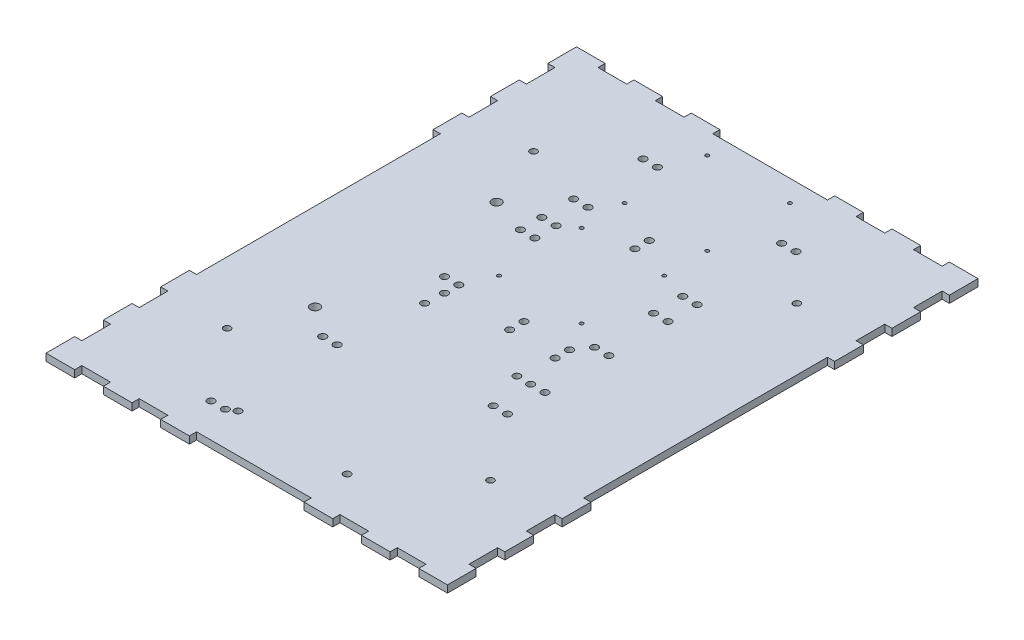
SolidWorks part; units mm, degrees
material "Acrylic (Medium-high impact)"
ref_plane "Front Plane" through (0, 0, 0) normal (0, 0, 1) x (1, 0, 0)
ref_plane "Top Plane" through (0, 0, 0) normal (0, 1, 0) x (1, 0, 0)
ref_plane "Right Plane" through (0, 0, 0) normal (1, 0, 0) x (0, 0, -1)
sketch "Sketch1" plane through (0, 0, 0) normal (0, 1, 0) x (1, 0, 0)
  line L0 (0, 209.55) -> (0, 196.85)
  line L1 (0, 0) -> (177.8, 0)
  line L2 (0, 0) -> (0, 234.95)
  line L3 (0, 234.95) -> (177.8, 234.95)
  line L4 (177.8, 0) -> (177.8, 234.95)
  line L5 (0, 234.95) -> (3.175, 234.95)
  line L6 (0, 234.95) -> (0, 0)
  line L7 (0, 0) -> (3.175, 0)
  line L8 (3.175, 234.95) -> (3.175, 0)
  line L9 (177.8, 234.95) -> (174.625, 234.95)
  line L10 (177.8, 234.95) -> (177.8, 0)
  line L11 (177.8, 0) -> (174.625, 0)
  line L12 (174.625, 234.95) -> (174.625, 0)
  line L13 (0, 234.95) -> (3.175, 234.95)
  line L14 (0, 234.95) -> (0, 222.25)
  line L15 (0, 222.25) -> (3.175, 222.25)
  line L16 (3.175, 234.95) -> (3.175, 222.25)
  line L17 (0, 209.55) -> (3.175, 209.55)
  line L18 (3.175, 209.55) -> (3.175, 196.85)
  line L19 (0, 196.85) -> (3.175, 196.85)
  line L20 (0, 184.15) -> (0, 171.45)
  line L21 (0, 184.15) -> (3.175, 184.15)
  line L22 (3.175, 184.15) -> (3.175, 171.45)
  line L23 (0, 171.45) -> (3.175, 171.45)
  line L24 (0, 117.475) -> (177.8, 117.475) construction
  line L25 (88.9, 234.95) -> (88.9, 0) construction
  line L26 (177.8, 171.45) -> (174.625, 171.45)
  line L27 (174.625, 184.15) -> (174.625, 171.45)
  line L28 (177.8, 184.15) -> (174.625, 184.15)
  line L29 (177.8, 184.15) -> (177.8, 171.45)
  line L30 (177.8, 196.85) -> (174.625, 196.85)
  line L31 (174.625, 209.55) -> (174.625, 196.85)
  line L32 (177.8, 209.55) -> (174.625, 209.55)
  line L33 (174.625, 234.95) -> (174.625, 222.25)
  line L34 (177.8, 222.25) -> (174.625, 222.25)
  line L35 (177.8, 234.95) -> (177.8, 222.25)
  line L36 (177.8, 234.95) -> (174.625, 234.95)
  line L37 (177.8, 234.95) -> (177.8, 0)
  line L38 (177.8, 234.95) -> (174.625, 234.95)
  line L39 (177.8, 209.55) -> (177.8, 196.85)
  line L40 (177.8, 25.4) -> (177.8, 38.1)
  line L41 (177.8, 0) -> (174.625, 0)
  line L42 (177.8, 0) -> (174.625, 0)
  line L43 (177.8, 0) -> (177.8, 12.7)
  line L44 (177.8, 12.7) -> (174.625, 12.7)
  line L45 (174.625, 0) -> (174.625, 12.7)
  line L46 (177.8, 25.4) -> (174.625, 25.4)
  line L47 (174.625, 25.4) -> (174.625, 38.1)
  line L48 (177.8, 38.1) -> (174.625, 38.1)
  line L49 (177.8, 50.8) -> (177.8, 63.5)
  line L50 (177.8, 50.8) -> (174.625, 50.8)
  line L51 (174.625, 50.8) -> (174.625, 63.5)
  line L52 (177.8, 63.5) -> (174.625, 63.5)
  line L53 (0, 63.5) -> (3.175, 63.5)
  line L54 (3.175, 50.8) -> (3.175, 63.5)
  line L55 (0, 50.8) -> (3.175, 50.8)
  line L56 (0, 50.8) -> (0, 63.5)
  line L57 (0, 38.1) -> (3.175, 38.1)
  line L58 (3.175, 25.4) -> (3.175, 38.1)
  line L59 (0, 25.4) -> (3.175, 25.4)
  line L60 (3.175, 0) -> (3.175, 12.7)
  line L61 (0, 12.7) -> (3.175, 12.7)
  line L62 (0, 0) -> (0, 12.7)
  line L63 (0, 0) -> (3.175, 0)
  line L64 (177.8, 0) -> (174.625, 0)
  line L65 (0, 0) -> (3.175, 0)
  line L66 (0, 0) -> (177.8, 0)
  line L67 (0, 25.4) -> (0, 38.1)
  dimension "D1" = 234.95
  dimension "D2" = 177.8
  dimension "D3" = 3.175
  dimension "D4" = 3.175
  dimension "D5" = 12.7
  dimension "D6" = 3.175
  dimension "D7" = 3
extrude "Boss-Extrude1" add sketch "Sketch1" along normal blind 3.175 contours L6 L55 L8 L53 | L6 L59 L8 L57 | L61 L2 L1 L8 | L6 L23 L8 L21 | L0 L19 L8 L17 | L6 L15 L8 L3 | L4 L44 L12 L1 | L37 L48 L12 L46 | L37 L52 L12 L50 | L34 L10 L3 L12 | L10 L32 L12 L30 | L10 L28 L12 L26 | L52 L12 L26 L27 L28 L30 L31 L32 L34 L33 L3 L8 L1 L45 L44 L46 L47 L48 L50 L51 region at (1.5875, 0, -203.2) region at (1.5875, 0, -228.6) region at (88.9, 0, -117.475) region at (1.5875, 0, -177.8) region at (1.5875, 0, -57.15) region at (176.2125, 0, -228.6) region at (1.5875, 0, -31.75) region at (176.2125, 0, -203.2) region at (1.5875, 0, -6.35) region at (176.2125, 0, -177.8) region at (176.2125, 0, -57.15) region at (176.2125, 0, -6.35) region at (176.2125, 0, -31.75)
sketch "Sketch2" plane through (0, 3.175, 0) normal (0, 1, 0) x (1, 0, 0)
  line L0 (3.175, 12.7) -> (30.5816, 12.7)
  line L1 (30.5816, 0) -> (30.5816, 234.95)
  line L3 (0, 0) -> (177.8, 0) construction
  line L4 (0, 234.95) -> (177.8, 234.95) construction
  line L5 (30.5816, 0) -> (30.5816, 14.0716)
  line L6 (30.5816, 14.0716) -> (30.5816, 49.6316)
  line L7 (3.175, 117.475) -> (174.625, 117.475) construction
  line L8 (3.175, 171.45) -> (3.175, 63.5) construction
  line L9 (174.625, 171.45) -> (174.625, 63.5) construction
  line L10 (88.9, 234.95) -> (88.9, 0) construction
  circle A0 centre (30.5816, 49.6316) radius 1.524
  circle A1 centre (147.2184, 49.6316) radius 1.524
  circle A2 centre (147.2184, 185.3184) radius 1.524
  circle A3 centre (30.5816, 185.3184) radius 1.524
  dimension "D4" = 3.048
  dimension "D1" = 27.4066
  dimension "D2" = 14.0716
  dimension "D3" = 35.56
extrude "Cut-Extrude1" cut sketch "Sketch2" against normal blind 3.175 and the other way through all contours A3 L1 | A3 L1 | L1 A0 L6 | L6 A0 L1 | A1 | A2 region at (29.9348, 3.175, -49.6316) region at (29.9348, 3.175, -185.3184) region at (31.2284, 3.175, -185.3184) region at (31.2284, 3.175, -49.6316) region at (147.2184, 3.175, -49.6316) region at (147.2184, 3.175, -185.3184)
sketch "Sketch3" plane through (0, 3.175, 0) normal (0, 1, 0) x (1, 0, 0)
  line L0 (88.9, 234.95) -> (88.9, 0) construction
  line L1 (0, 234.95) -> (177.8, 234.95) construction
  line L2 (0, 0) -> (177.8, 0) construction
  line L4 (88.9, 234.95) -> (70.6, 234.95)
  line L5 (88.9, 234.95) -> (88.9, 222.25)
  line L6 (88.9, 222.25) -> (70.6, 222.25)
  line L7 (70.6, 234.95) -> (70.6, 222.25)
  line L8 (70.6, 222.25) -> (107.2, 222.25)
  line L9 (70.6, 222.25) -> (70.6, 185.65)
  line L10 (70.6, 185.65) -> (107.2, 185.65)
  line L11 (107.2, 222.25) -> (107.2, 185.65)
  line L12 (70.6, 166.6) -> (107.2, 166.6)
  line L13 (70.6, 166.6) -> (70.6, 130)
  line L14 (70.6, 130) -> (107.2, 130)
  line L15 (107.2, 166.6) -> (107.2, 130)
  circle A0 centre (70.6, 222.25) radius 0.8
  circle A1 centre (107.2, 222.25) radius 0.8
  circle A2 centre (70.6, 185.65) radius 0.8
  circle A3 centre (107.2, 185.65) radius 0.8
  circle A4 centre (70.6, 166.6) radius 0.8
  circle A5 centre (107.2, 166.6) radius 0.8
  circle A6 centre (70.6, 130) radius 0.8
  circle A7 centre (107.2, 130) radius 0.8
  dimension "D4" = 1.6
  dimension "D5" = 1.6
  dimension "D6" = 1.6
  dimension "D7" = 1.6
  dimension "D8" = 36.6
  dimension "D10" = 1.6
  dimension "D11" = 1.6
  dimension "D12" = 1.6
  dimension "D13" = 1.6
  dimension "D1" = 12.7
  dimension "D2" = 18.3
  dimension "D3" = 36.6
  dimension "D9" = 19.05
extrude "Cut-Extrude2" cut sketch "Sketch3" against normal blind 5.715 contours L8 A0 L7 | L7 A0 L9 | L9 A0 L8 | L8 A1 L11 | L11 A1 L8 | L10 A2 L9 | L9 A2 L10 | L11 A3 L10 | L10 A3 L11 | L13 A4 L12 | L12 A4 L13 | L12 A5 L15 | L15 A5 L12 | L14 A6 L13 | L13 A6 L14 | L15 A7 L14 | L14 A7 L15 region at (70.9395, 3.175, -222.5895) region at (70.2605, 3.175, -222.25) region at (70.9395, 3.175, -221.9105) region at (107.3132, 3.175, -222.3632) region at (106.8605, 3.175, -221.9105) region at (70.9395, 3.175, -185.9895) region at (70.4868, 3.175, -185.5368) region at (107.3132, 3.175, -185.5368) region at (106.8605, 3.175, -185.9895) region at (70.4868, 3.175, -166.7132) region at (70.9395, 3.175, -166.2605) region at (107.3132, 3.175, -166.7132) region at (106.8605, 3.175, -166.2605) region at (70.9395, 3.175, -130.3395) region at (70.4868, 3.175, -129.8868) region at (107.3132, 3.175, -129.8868) region at (106.8605, 3.175, -130.3395)
sketch "Sketch4" plane through (0, 3.175, 0) normal (0, 1, 0) x (1, 0, 0)
  line L0 (88.9, 0) -> (88.9, 20.32) construction
  line L1 (0, 0) -> (177.8, 0) construction
  line L2 (88.9, 20.32) -> (64.7319, 20.32) construction
  line L3 (64.7319, 20.32) -> (64.7319, 95.4532) construction
  line L4 (64.7319, 20.32) -> (113.0681, 20.32) construction
  line L5 (113.0681, 20.32) -> (113.0681, 102.9462) construction
  circle A0 centre (64.7319, 20.32) radius 1.5621
  circle A3 centre (113.0681, 20.32) radius 1.5621
  circle A4 centre (64.7319, 102.9462) radius 1.5621
  circle A5 centre (113.0681, 95.4532) radius 1.5621
  dimension "D3" = 3.1242
  dimension "D4" = 75.1332
  dimension "D9" = 3.1242
  dimension "D1" = 20.32
  dimension "D2" = 24.1681
  dimension "D6" = 48.3362
  dimension "D7" = 82.6262
extrude "Cut-Extrude3" cut sketch "Sketch4" against normal blind 10.16 contours A3 | A0 | A4 | A5 region at (64.7319, 3.175, -20.32) region at (113.0681, 3.175, -20.32) region at (64.7319, 3.175, -102.9462) region at (113.0681, 3.175, -95.4532)
sketch "Sketch5" plane through (0, 3.175, 0) normal (0, 1, 0) x (1, 0, 0)
  line L0 (88.9, 0) -> (88.9, 18.3402) construction
  line L1 (0, 0) -> (177.8, 0) construction
  line L3 (0, 0) -> (12.7, 0)
  line L4 (0, 0) -> (0, 3.175)
  line L5 (0, 3.175) -> (12.7, 3.175)
  line L6 (12.7, 0) -> (12.7, 3.175)
  line L10 (25.4, 3.175) -> (38.1, 3.175)
  line L11 (25.4, 0) -> (38.1, 0)
  line L12 (38.1, 0) -> (38.1, 3.175)
  line L13 (25.4, 0) -> (25.4, 3.175)
  line L14 (50.8, 3.175) -> (63.5, 3.175)
  line L15 (50.8, 0) -> (63.5, 0)
  line L16 (63.5, 0) -> (63.5, 3.175)
  line L17 (50.8, 0) -> (50.8, 3.175)
  line L18 (0, 3.175) -> (177.8, 3.175)
  line L19 (127, 0) -> (127, 3.175)
  line L20 (114.3, 0) -> (114.3, 3.175)
  line L21 (127, 0) -> (114.3, 0)
  line L22 (127, 3.175) -> (114.3, 3.175)
  line L23 (152.4, 0) -> (152.4, 3.175)
  line L24 (139.7, 0) -> (139.7, 3.175)
  line L25 (152.4, 0) -> (139.7, 0)
  line L26 (152.4, 3.175) -> (139.7, 3.175)
  line L27 (165.1, 0) -> (165.1, 3.175)
  line L28 (177.8, 3.175) -> (165.1, 3.175)
  line L29 (177.8, 0) -> (177.8, 3.175)
  line L30 (177.8, 0) -> (165.1, 0)
  line L63 (0, 63.5) -> (0, 50.8)
  line L64 (0, 50.8) -> (3.175, 50.8)
  line L65 (3.175, 50.8) -> (3.175, 38.1)
  line L66 (3.175, 38.1) -> (0, 38.1)
  line L67 (0, 38.1) -> (0, 25.4)
  line L68 (0, 25.4) -> (3.175, 25.4)
  line L69 (3.175, 25.4) -> (3.175, 12.7)
  line L70 (3.175, 12.7) -> (0, 12.7)
  line L71 (0, 12.7) -> (0, 0)
  line L72 (0, 0) -> (177.8, 0)
  line L73 (177.8, 0) -> (177.8, 12.7)
  line L74 (177.8, 12.7) -> (174.625, 12.7)
  line L75 (174.625, 12.7) -> (174.625, 25.4)
  line L76 (174.625, 25.4) -> (177.8, 25.4)
  line L77 (177.8, 25.4) -> (177.8, 38.1)
  line L78 (177.8, 38.1) -> (174.625, 38.1)
  line L79 (174.625, 38.1) -> (174.625, 50.8)
  line L80 (174.625, 50.8) -> (177.8, 50.8)
  line L81 (177.8, 50.8) -> (177.8, 63.5)
  line L82 (177.8, 63.5) -> (174.625, 63.5)
  line L83 (174.625, 63.5) -> (174.625, 171.45)
  line L84 (174.625, 171.45) -> (177.8, 171.45)
  line L85 (177.8, 171.45) -> (177.8, 184.15)
  line L86 (177.8, 184.15) -> (174.625, 184.15)
  line L87 (174.625, 184.15) -> (174.625, 196.85)
  line L88 (174.625, 196.85) -> (177.8, 196.85)
  line L89 (177.8, 196.85) -> (177.8, 209.55)
  line L90 (177.8, 209.55) -> (174.625, 209.55)
  line L91 (174.625, 209.55) -> (174.625, 222.25)
  line L92 (174.625, 222.25) -> (177.8, 222.25)
  line L93 (177.8, 222.25) -> (177.8, 234.95)
  line L94 (177.8, 234.95) -> (0, 234.95)
  line L95 (0, 234.95) -> (0, 222.25)
  line L96 (0, 222.25) -> (3.175, 222.25)
  line L97 (3.175, 222.25) -> (3.175, 209.55)
  line L98 (3.175, 209.55) -> (0, 209.55)
  line L99 (0, 209.55) -> (0, 196.85)
  line L100 (0, 196.85) -> (3.175, 196.85)
  line L101 (3.175, 196.85) -> (3.175, 184.15)
  line L102 (3.175, 184.15) -> (0, 184.15)
  line L103 (0, 184.15) -> (0, 171.45)
  line L104 (0, 171.45) -> (3.175, 171.45)
  line L105 (3.175, 171.45) -> (3.175, 63.5)
  line L106 (3.175, 63.5) -> (0, 63.5)
  line L107 (0, 63.5) -> (0, 50.8)
  line L108 (0, 50.8) -> (3.175, 50.8)
  line L109 (3.175, 50.8) -> (3.175, 38.1)
  line L110 (3.175, 38.1) -> (0, 38.1)
  line L111 (0, 38.1) -> (0, 25.4)
  line L112 (0, 25.4) -> (3.175, 25.4)
  line L113 (3.175, 25.4) -> (3.175, 12.7)
  line L114 (3.175, 12.7) -> (0, 12.7)
  line L115 (0, 12.7) -> (0, 0)
  line L116 (0, 0) -> (177.8, 0)
  line L117 (177.8, 0) -> (177.8, 12.7)
  line L118 (177.8, 12.7) -> (174.625, 12.7)
  line L119 (174.625, 12.7) -> (174.625, 25.4)
  line L120 (174.625, 25.4) -> (177.8, 25.4)
  line L121 (177.8, 25.4) -> (177.8, 38.1)
  line L122 (177.8, 38.1) -> (174.625, 38.1)
  line L123 (174.625, 38.1) -> (174.625, 50.8)
  line L124 (174.625, 50.8) -> (177.8, 50.8)
  line L125 (177.8, 50.8) -> (177.8, 63.5)
  line L126 (177.8, 63.5) -> (174.625, 63.5)
  line L127 (174.625, 63.5) -> (174.625, 171.45)
  line L128 (174.625, 171.45) -> (177.8, 171.45)
  line L129 (177.8, 171.45) -> (177.8, 184.15)
  line L130 (177.8, 184.15) -> (174.625, 184.15)
  line L131 (174.625, 184.15) -> (174.625, 196.85)
  line L132 (174.625, 196.85) -> (177.8, 196.85)
  line L133 (177.8, 196.85) -> (177.8, 209.55)
  line L134 (177.8, 209.55) -> (174.625, 209.55)
  line L135 (174.625, 209.55) -> (174.625, 222.25)
  line L136 (174.625, 222.25) -> (177.8, 222.25)
  line L137 (177.8, 222.25) -> (177.8, 234.95)
  line L138 (177.8, 234.95) -> (0, 234.95)
  line L139 (0, 234.95) -> (0, 222.25)
  line L140 (0, 222.25) -> (3.175, 222.25)
  line L141 (3.175, 222.25) -> (3.175, 209.55)
  line L142 (3.175, 209.55) -> (0, 209.55)
  line L143 (0, 209.55) -> (0, 196.85)
  line L144 (0, 196.85) -> (3.175, 196.85)
  line L145 (3.175, 196.85) -> (3.175, 184.15)
  line L146 (3.175, 184.15) -> (0, 184.15)
  line L147 (0, 184.15) -> (0, 171.45)
  line L148 (0, 171.45) -> (3.175, 171.45)
  line L149 (3.175, 171.45) -> (3.175, 63.5)
  line L150 (3.175, 63.5) -> (0, 63.5)
  point P22 (88.9, 3.175)
  dimension "D1" = 3.175
  dimension "D2" = 12.7
  dimension "D4" = 0
  dimension "D3" = 3
extrude "Cut-Extrude4" cut sketch "Sketch5" against normal blind 7.62 contours L6 L116 L13 L18 | L12 L116 L17 L18 | L116 L0 L18 L16 | L0 L116 L20 L18 | L19 L116 L24 L18 | L23 L116 L27 L18 region at (76.2, 3.175, -1.5875) region at (101.6, 3.175, -1.5875) region at (44.45, 3.175, -1.5875) region at (133.35, 3.175, -1.5875) region at (19.05, 3.175, -1.5875) region at (158.75, 3.175, -1.5875)
ref_plane "Plane2" through (0, 0, -117.475) normal (0, 0, 1) x (1, 0, 0)
mirror "Mirror1" about plane through (0, 0, -117.475) normal (0, 0, 1) of "Cut-Extrude4"
sketch "Sketch7" plane through (0, 0, 0) normal (0, -1, 0) x (1, 0, 0)
  line L0 (3.175, -117.475) -> (41.8719, -117.475) construction
  line L1 (3.175, -171.45) -> (3.175, -63.5) construction
  line L2 (41.8719, -3.175) -> (41.8719, -231.775) construction
  line L3 (38.1, -3.175) -> (50.8, -3.175) construction
  line L4 (38.1, -231.775) -> (50.8, -231.775) construction
  circle A0 centre (64.7319, -102.9462) radius 1.5621 construction
  circle A1 centre (41.8719, -77.2795) radius 2.0955
  circle A2 centre (41.8719, -157.6705) radius 2.0955
  dimension "D2" = 4.191
  dimension "D1" = 22.86
  dimension "D3" = 40.1955
extrude "Cut-Extrude5" cut sketch "Sketch7" against normal blind 7.62
sketch "Sketch17" plane through (0, 3.175, 0) normal (0, 1, 0) x (1, 0, 0)
  line L0 (91.6678, 361.6416) -> (457.6678, 361.6416) construction
  line L1 (133.0743, 97.8218) -> (123.5696, 97.8218)
  line L2 (123.5696, 97.8218) -> (123.5696, 114.4551)
  line L3 (123.5696, 114.4551) -> (49.0171, 114.4551)
  line L4 (96.8376, 126.336) -> (96.8376, 114.4551)
  line L5 (41.4006, 69.0107) -> (41.4006, 10.2003)
  line L6 (41.4006, 10.2003) -> (58.8967, 10.2003)
  line L7 (96.8376, 182.0344) -> (96.8376, 173.9503)
  line L8 (96.8376, 173.9503) -> (41.7, 173.9503)
  line L9 (41.7, 173.9503) -> (41.7, 165.8662)
  line L10 (152.4827, 75.7429) -> (123.5696, 75.7429)
  line L11 (123.5696, 75.7429) -> (123.5696, 155.3867)
  line L12 (123.5696, 155.3867) -> (109.9661, 155.3867)
  line L13 (21.0405, 75.7429) -> (24.3341, 75.7429)
  line L14 (24.3341, 75.7429) -> (24.3341, 168.2615)
  line L15 (24.3341, 168.2615) -> (60.8624, 168.2615)
  line L16 (60.8624, 168.2615) -> (60.8624, 155.3867)
  line L17 (60.8624, 155.3867) -> (68.0483, 155.3867)
  line L18 (21.0405, 157.782) -> (24.3341, 157.782)
  line L19 (24.3341, 157.782) -> (24.3341, 168.2615)
  line L20 (60.8624, 168.2615) -> (60.8624, 211.3769)
  line L21 (60.8624, 211.3769) -> (68.0483, 211.3769)
  line L22 (109.9661, 211.3769) -> (123.5696, 211.3769)
  line L23 (155.0958, 157.782) -> (123.5696, 157.782)
  line L24 (123.5696, 157.782) -> (123.5696, 211.3769)
  line L25 (36.6766, 179.7822) -> (58.8967, 179.7822)
  line L26 (58.8967, 179.7822) -> (58.8967, 80.6555)
  line L27 (58.8967, 80.6555) -> (75.4402, 80.6555)
  line L28 (36.6766, 52.3642) -> (75.4402, 52.3642)
  line L29 (141.0042, 52.3642) -> (103.507, 52.3642)
  line L30 (141.0042, 179.7822) -> (120.7991, 179.7822)
  line L31 (120.7991, 179.7822) -> (120.7991, 80.6555)
  line L32 (120.7991, 80.6555) -> (103.507, 80.6555)
  line L33 (65.2467, 117.5685) -> (65.2467, 111.2185) construction
  line L34 (114.6482, 117.1902) -> (114.6482, 110.8402) construction
  line L35 (119.2416, 123.6782) -> (125.5916, 123.6782) construction
  line L36 (119.2416, 149.8246) -> (125.5916, 149.8246) construction
  line L37 (119.2416, 162.7601) -> (125.5916, 162.7601) construction
  line L38 (120.7991, 205.0032) -> (127.1491, 205.0032) construction
  line L39 (57.7399, 206.696) -> (64.0899, 206.696) construction
  line L40 (57.7399, 175.9435) -> (64.0899, 175.9435) construction
  line L41 (57.7399, 152.3855) -> (64.0899, 152.3855) construction
  line L42 (57.7399, 161.8241) -> (64.0899, 161.8241) construction
  line L43 (58.8967, 117.5685) -> (65.2467, 117.5685) construction
  line L44 (54.8927, 67.6581) -> (61.2427, 67.6581) construction
  line L45 (119.2416, 95.4017) -> (125.5916, 95.4017) construction
  line L46 (119.2416, 78.8212) -> (125.5916, 78.8212) construction
  line L47 (54.8927, 18.1834) -> (61.2427, 18.1834) construction
  line L48 (90.4002, 176.7528) -> (90.4002, 170.4028) construction
  line L49 (93.7187, 117.9618) -> (93.7187, 111.6118) construction
  circle A0 centre (65.2467, 117.5685) radius 1.5875
  circle A1 centre (65.2467, 111.2185) radius 1.5875
  circle A2 centre (114.6482, 117.1902) radius 1.5875
  circle A3 centre (114.6482, 110.8402) radius 1.5875
  circle A4 centre (125.5916, 123.6782) radius 1.5875
  circle A5 centre (119.2416, 123.6782) radius 1.5875
  circle A6 centre (125.5916, 149.8246) radius 1.5875
  circle A7 centre (119.2416, 149.8246) radius 1.5875
  circle A8 centre (125.5916, 162.7601) radius 1.5875
  circle A9 centre (119.2416, 162.7601) radius 1.5875
  circle A10 centre (127.1491, 205.0032) radius 1.5875
  circle A11 centre (120.7991, 205.0032) radius 1.5875
  circle A12 centre (64.0899, 206.696) radius 1.5875
  circle A13 centre (57.7399, 206.696) radius 1.5875
  circle A14 centre (64.0899, 175.9435) radius 1.5875
  circle A15 centre (57.7399, 175.9435) radius 1.5875
  circle A16 centre (64.0899, 152.3855) radius 1.5875
  circle A17 centre (57.7399, 152.3855) radius 1.5875
  circle A18 centre (64.0899, 161.8241) radius 1.5875
  circle A19 centre (57.7399, 161.8241) radius 1.5875
  circle A20 centre (65.2467, 117.5685) radius 1.5875
  circle A21 centre (58.8967, 117.5685) radius 1.5875
  circle A22 centre (61.2427, 67.6581) radius 1.5875
  circle A23 centre (54.8927, 67.6581) radius 1.5875
  circle A24 centre (125.5916, 95.4017) radius 1.5875
  circle A25 centre (119.2416, 95.4017) radius 1.5875
  circle A26 centre (125.5916, 78.8212) radius 1.5875
  circle A27 centre (119.2416, 78.8212) radius 1.5875
  circle A28 centre (61.2427, 18.1834) radius 1.5875
  circle A29 centre (54.8927, 18.1834) radius 1.5875
  circle A30 centre (90.4002, 176.7528) radius 1.5875
  circle A31 centre (90.4002, 170.4028) radius 1.5875
  circle A32 centre (93.7187, 117.9618) radius 1.5875
  circle A33 centre (93.7187, 111.6118) radius 1.5875
  point P51 (119.2416, 123.6782)
  point P57 (201.7594, 146.4187)
  point P59 (196.1096, 145.6351)
  point P64 (119.2416, 149.8246)
  point P69 (118.4159, 165.5124)
  point P70 (119.2416, 162.7601)
  point P75 (120.7991, 205.0032)
  point P80 (57.7399, 206.696)
  point P85 (57.7399, 175.9435)
  point P90 (57.7399, 152.3855)
  point P95 (57.7399, 161.8241)
  point P100 (58.8188, 116.8658)
  point P105 (54.8927, 67.6581)
  point P110 (119.2416, 95.4017)
  point P115 (119.2416, 78.8212)
  point P116 (65.1635, 122.4028)
  point P117 (0, 0)
  point P118 (0, 0)
  point P119 (65.2467, 117.9713)
  point P123 (54.8927, 18.1834)
  point P128 (90.4002, 170.4028)
  dimension "D1" = 3.175
  dimension "D2" = 3.175
  dimension "D4" = 6.35
  dimension "D6" = 3.175
  dimension "D7" = 3.175
  dimension "D9" = 3.175
  dimension "D10" = 3.175
  dimension "D12" = 3.175
  dimension "D13" = 3.175
  dimension "D15" = 3.175
  dimension "D16" = 3.175
  dimension "D18" = 3.175
  dimension "D19" = 3.175
  dimension "D21" = 3.175
  dimension "D22" = 3.175
  dimension "D24" = 3.175
  dimension "D25" = 3.175
  dimension "D27" = 3.175
  dimension "D28" = 3.175
  dimension "D30" = 3.175
  dimension "D31" = 3.175
  dimension "D33" = 3.175
  dimension "D34" = 3.175
  dimension "D36" = 3.175
  dimension "D37" = 3.175
  dimension "D39" = 3.175
  dimension "D40" = 3.175
  dimension "D42" = 3.175
  dimension "D43" = 3.175
  dimension "D3" = 6.35
  dimension "D5" = 6.35
  dimension "D8" = 6.35
  dimension "D11" = 6.35
  dimension "D14" = 6.35
  dimension "D17" = 6.35
  dimension "D20" = 6.35
  dimension "D23" = 6.35
  dimension "D26" = 6.35
  dimension "D29" = 6.35
  dimension "D32" = 6.35
  dimension "D35" = 6.35
  dimension "D38" = 6.35
  dimension "D41" = 6.35
  dimension "D44" = 6.35
  dimension "D45" = 6.35
extrude "Cut-Extrude6" cut sketch "Sketch17" against normal blind 2.54 contours L26 A17 | L26 A17 | A16 | L26 A19 | L26 A19 | A18 | L26 A15 | L26 A15 | A14 | A13 | A12 | A11 | A10 | L26 A21 | A1 | A23 | A22 | A29 | A28 | A27 | A26 | L31 A25 | A24 | A33 | A32 | A3 | L31 A5 | A4 | A2 | L31 A9 | A8 | A6 | L31 A7 | A30 | A31 | A21 | A0 region at (119.2392, 3.175, -95.4017) region at (57.6221, 3.175, -175.9435) region at (59.0712, 3.175, -175.9435) region at (57.6221, 3.175, -161.8241) region at (59.0712, 3.175, -161.8241) region at (57.6221, 3.175, -152.3855) region at (59.0712, 3.175, -152.3855) region at (59.5705, 3.175, -117.5685) region at (119.2392, 3.175, -162.7601) region at (119.2392, 3.175, -123.6782) region at (119.2392, 3.175, -149.8246) region at (65.2467, 3.175, -111.2185) region at (114.6482, 3.175, -117.1902) region at (114.6482, 3.175, -110.8402) region at (125.5916, 3.175, -123.6782) region at (125.5916, 3.175, -149.8246) region at (125.5916, 3.175, -162.7601) region at (127.1491, 3.175, -205.0032) region at (120.7991, 3.175, -205.0032) region at (64.0899, 3.175, -206.696) region at (57.7399, 3.175, -206.696) region at (64.0899, 3.175, -175.9435) region at (64.0899, 3.175, -152.3855) region at (64.0899, 3.175, -161.8241) region at (61.2427, 3.175, -67.6581) region at (54.8927, 3.175, -67.6581) region at (125.5916, 3.175, -95.4017) region at (125.5916, 3.175, -78.8212) region at (119.2416, 3.175, -78.8212) region at (61.2427, 3.175, -18.1834) region at (54.8927, 3.175, -18.1834) region at (93.7187, 3.175, -117.9618) region at (93.7187, 3.175, -111.6118)
